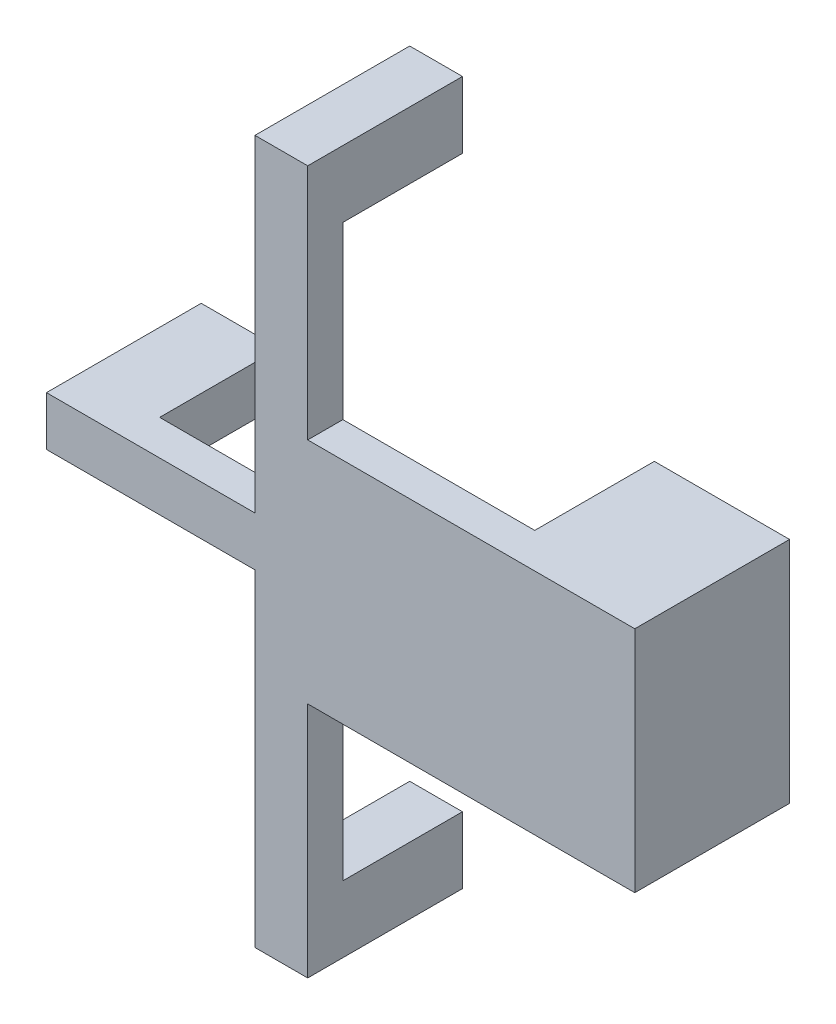
SolidWorks part; units mm, degrees
ref_plane "正面" through (0, 0, 0) normal (0, 0, 1) x (1, 0, 0)
ref_plane "平面" through (0, 0, 0) normal (0, 1, 0) x (1, 0, 0)
ref_plane "右側面" through (0, 0, 0) normal (1, 0, 0) x (0, 0, -1)
sketch "ｽｹｯﾁ1" plane through (0, 0, 0) normal (0, 0, 1) x (1, 0, 0)
  line L1 (-14.8577, -7.9) -> (-10.421, -7.9)
  line L2 (-14.8577, -7.9) -> (-14.8577, -5.1)
  line L3 (-14.8577, -5.1) -> (-10.421, -5.1)
  line L4 (-10.421, -7.9) -> (-10.421, -5.1)
  line L6 (10.9106, 0) -> (18.6, 0)
  line L7 (10.9106, -13) -> (18.6, -13)
  line L8 (0, 13.5) -> (0, 9.7115)
  line L9 (-3, 9.7115) -> (-3, 13.5)
  line L10 (-3, -22.7115) -> (0, -22.7115)
  line L11 (-3, -26.5) -> (0, -26.5)
  line L12 (-3, 13.5) -> (0, 13.5)
  line L13 (-3, 9.7115) -> (0, 9.7115)
  line L14 (-3, -5.1) -> (-3, -7.9) construction
  line L15 (-3, -6.5) -> (-10.421, -6.5) construction
  line L16 (-3, -22.7115) -> (-3, -26.5)
  line L17 (0, -26.5) -> (0, -22.7115)
  line L18 (10.9106, 0) -> (10.9106, -13)
  line L19 (18.6, 0) -> (18.6, -13)
extrude "ﾎﾞｽ - 押し出し1" add sketch "ｽｹｯﾁ1" against normal blind 8.8
sketch "ｽｹｯﾁ2" plane through (0, 0, 0) normal (0, 0, 1) x (1, 0, 0)
  line L0 (0, -13) -> (18.6, -13) construction
  line L1 (0, 0) -> (18.6, 0) construction
  line L2 (0, -13) -> (0, -33.8) construction
  line L3 (-3, -26.5) -> (0, -26.5) construction
  line L4 (-3, -7.9) -> (-3, -26.5) construction
  line L5 (-3, -5.1) -> (-3, 13.5) construction
  line L6 (0, 0) -> (0, 20.8) construction
  line L7 (0, 13.5) -> (-3, 13.5) construction
  line L8 (18.6, -13) -> (18.6, 0) construction
  line L9 (0, -13) -> (18.6, -13)
  line L10 (0, 0) -> (18.6, 0)
  line L11 (0, -13) -> (0, -26.5)
  line L12 (-3, -26.5) -> (0, -26.5)
  line L13 (-3, -7.9) -> (-3, -26.5)
  line L14 (-3, -5.1) -> (-3, 13.5)
  line L15 (0, 0) -> (0, 13.5)
  line L16 (0, 13.5) -> (-3, 13.5)
  line L17 (18.6, -13) -> (18.6, 0)
  line L19 (-14.8577, -5.1) -> (-14.8577, -7.9) construction
  line L20 (-14.8577, -7.9) -> (-3, -7.9)
  line L21 (-14.8577, -7.9) -> (-14.8577, -5.1)
  line L22 (-14.8577, -5.1) -> (-3, -5.1)
extrude "ﾎﾞｽ - 押し出し2" add sketch "ｽｹｯﾁ2" against normal blind 2
combine bodies "組み合わせ1" operation type add bodies to combine 105 104
